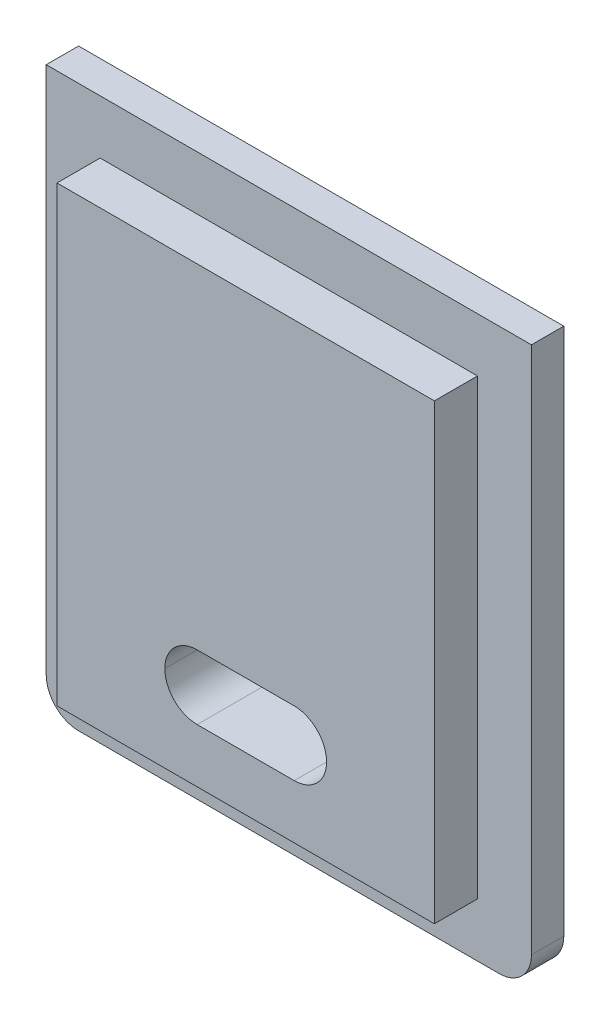
SolidWorks part; units mm, degrees
material "PE High Density"
ref_plane "Front Plane" through (0, 0, 0) normal (0, 0, 1) x (1, 0, 0)
ref_plane "Top Plane" through (0, 0, 0) normal (0, 1, 0) x (1, 0, 0)
ref_plane "Right Plane" through (0, 0, 0) normal (1, 0, 0) x (0, 0, -1)
sketch "Sketch1" plane through (0, 0, 0) normal (0, 0, 1) x (1, 0, 0)
  line L1 (0, 0) -> (45, 0)
  line L2 (0, 0) -> (0, 52)
  line L3 (0, 52) -> (45, 52)
  line L4 (45, 0) -> (45, 52)
  dimension "D1" = 45
  dimension "D2" = 52
extrude "Boss-Extrude1" add sketch "Sketch1" along normal blind 3
sketch "Sketch2" plane through (0, 0, 3) normal (0, 0, 1) x (1, 0, 0)
  line L0 (22.5, 52) -> (22.5, 0) construction
  line L1 (45, 52) -> (0, 52) construction
  line L2 (0, 0) -> (45, 0) construction
  line L4 (5, 47) -> (40, 47)
  line L5 (5, 47) -> (5, 5)
  line L6 (5, 5) -> (40, 5)
  line L7 (40, 47) -> (40, 5)
  line L8 (5, 47) -> (40, 5) construction
  line L9 (5, 5) -> (40, 47) construction
  point P6 (22.5, 26)
  dimension "D1" = 42
  dimension "D2" = 35
extrude "Boss-Extrude2" add sketch "Sketch2" along normal blind 4
sketch "Sketch3" plane through (0, 0, 7) normal (0, 0, 1) x (1, 0, 0)
  line L0 (22.5, 47) -> (22.5, 5) construction
  line L1 (15, 10) -> (30, 10)
  line L2 (15, 10) -> (15, 16)
  line L3 (15, 16) -> (30, 16)
  line L4 (30, 10) -> (30, 16)
  line L5 (40, 47) -> (5, 47) construction
  line L6 (5, 5) -> (40, 5) construction
  dimension "D1" = 15
  dimension "D2" = 6
  dimension "D3" = 5
extrude "Cut-Extrude1" cut sketch "Sketch3" against normal through all
fillet "Fillet1" radius 3 6 edges at (30, 10, 3.5) (15, 10, 3.5) (30, 16, 3.5) (15, 16, 3.5) (45, 0, 1.5) (0, 0, 1.5)
